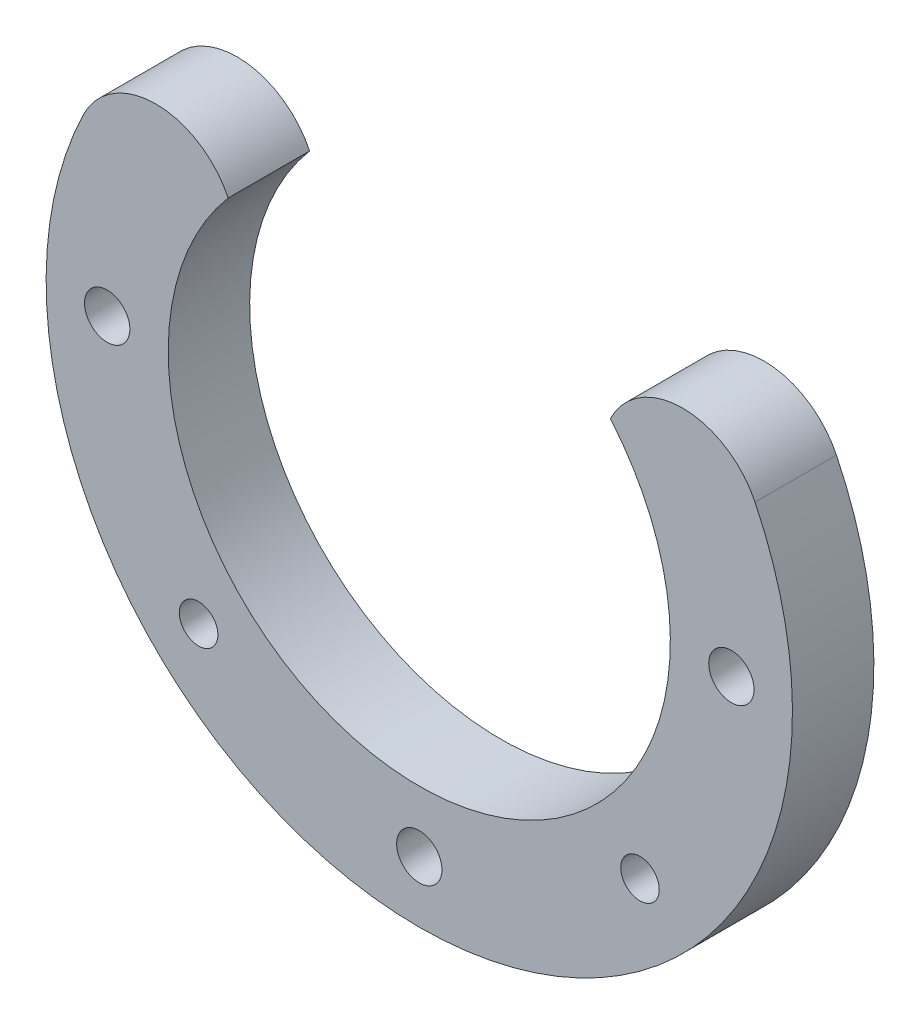
SolidWorks part; units mm, degrees
ref_plane "Front Plane" through (0, 0, 0) normal (0, 0, 1) x (1, 0, 0)
ref_plane "Top Plane" through (0, 0, 0) normal (0, 1, 0) x (1, 0, 0)
ref_plane "Right Plane" through (0, 0, 0) normal (1, 0, 0) x (0, 0, -1)
sketch "Sketch1" plane through (0, 0, 0) normal (0, 0, 1) x (1, 0, 0)
  line L0 (-24.7437, 12) -> (24.7437, 12) construction
  line L1 (0, 0) -> (0, 27.5) construction
  arc A0 (-24.7437, 12) -> (24.7437, 12) centre (0, 0) ccw
  arc A1 (-14.0801, 12) -> (14.0801, 12) centre (0, 0) ccw
  arc A2 (-24.7437, 12) -> (-14.0801, 12) centre (-19.4119, 9.4142) cw
  arc A3 (24.7437, 12) -> (14.0801, 12) centre (19.4119, 9.4142) ccw
  circle A4 centre (0, -23) radius 1.75
  circle A5 centre (0, 0) radius 23 construction
  circle A6 centre (-16.2635, -16.2635) radius 1.5
  circle A7 centre (-23, 0) radius 1.75
  circle A8 centre (-16.2635, 16.2635) radius 1.5 construction
  circle A9 centre (0, 23) radius 1.75 construction
  circle A10 centre (16.2635, 16.2635) radius 1.5 construction
  circle A11 centre (23, 0) radius 1.75
  circle A12 centre (16.2635, -16.2635) radius 1.5
  dimension "D1" = 55
  dimension "D2" = 37
  dimension "D4" = 46
  dimension "D5" = 3.5
  dimension "D6" = 3
  dimension "D3" = 12
  dimension "D8" = 45
  dimension "D7" = 4
extrude "Boss-Extrude1" add sketch "Sketch1" along normal blind 6
ref_axis "Axis1" through (14.0801, 12, 6) along (1, 0, 0)
other "Move Face1" face at (-21.25, 0, 6) face at (1.75, -23, 6) face at (-14.7635, -16.2635, 6) face at (24.75, 0, 6) face at (17.7635, -16.2635, 6) offset 0.08 parameters "D1"=0.08
